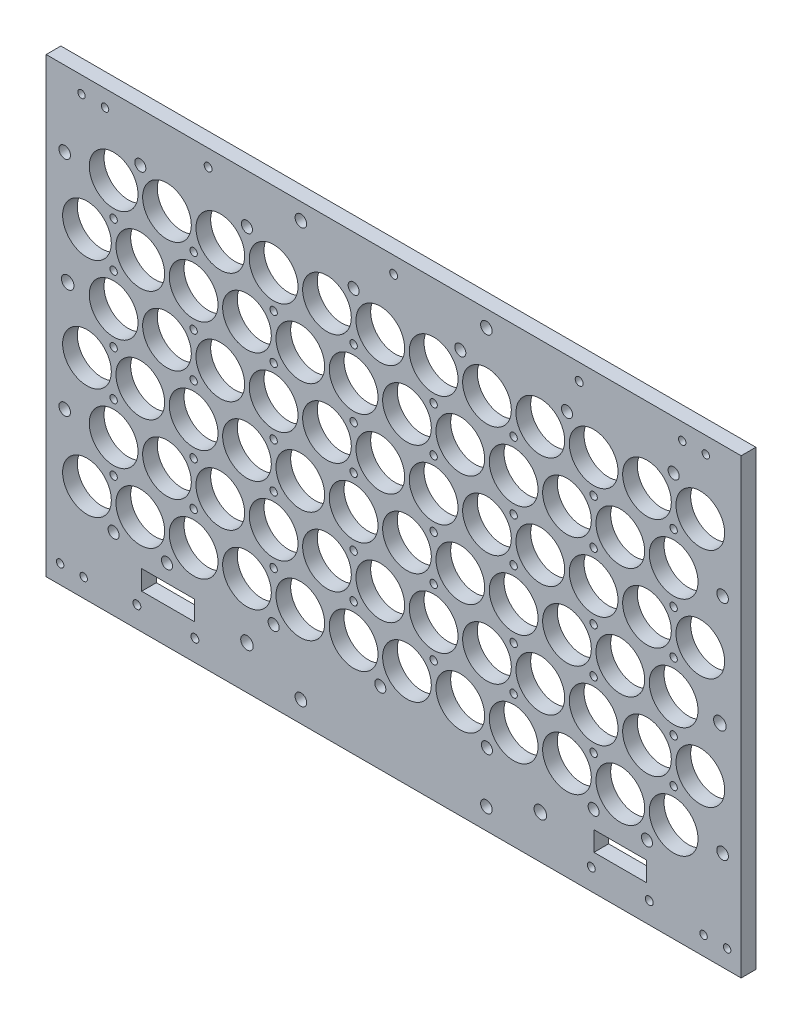
SolidWorks part; units mm, degrees
material "ABS"
ref_plane "X-Y Datum" through (0, 0, 0) normal (0, 0, 1) x (1, 0, 0)
ref_plane "X-Z Datum" through (0, 0, 0) normal (0, 1, 0) x (1, 0, 0)
ref_plane "Y-Z Datum" through (0, 0, 0) normal (1, 0, 0) x (0, 0, -1)
sketch "Sketch1" plane through (0, 0, 0) normal (0, 0, 1) x (1, 0, 0)
  line L1 (-143.025, 70.775) -> (143.025, 70.775)
  line L2 (-143.025, 70.775) -> (-143.025, -70.775)
  line L3 (-143.025, -70.775) -> (143.025, -70.775)
  line L4 (143.025, 70.775) -> (143.025, -70.775)
  line L5 (-143.025, 70.775) -> (143.025, -70.775) construction
  line L6 (-143.025, -70.775) -> (143.025, 70.775) construction
  line L13 (-149.85, -102.6) -> (149.85, -102.6)
  line L14 (-149.85, 91.65) -> (149.85, 91.65)
  line L15 (-149.85, 91.65) -> (-149.85, -102.6)
  line L16 (149.85, 91.65) -> (149.85, -102.6)
  line L17 (149.85, 70.775) -> (149.85, -70.775) construction
  line L18 (-143.025, 91.65) -> (143.025, 91.65) construction
  line L19 (-143.025, -102.6) -> (143.025, -102.6) construction
  line L20 (-149.85, 70.775) -> (-149.85, -70.775) construction
  line L21 (-132.25, -60) -> (-109.25, -60) construction
  circle A0 centre (-132.25, -60) radius 10.775
  circle A1 centre (-109.25, -60) radius 10.775 construction
  circle A2 centre (-120.75, -36) radius 10.775
  point P0 (0, 0)
  point P16 (-120.75, -60)
  dimension "D1" = 21.55
  dimension "D2" = 23
  dimension "D3" = 24
  dimension "D5" = 141.55
  dimension "D6" = 286.05
  dimension "D7" = 31.825
  dimension "D8" = 20.875
  dimension "D9" = 6.825
  dimension "D10" = 6.825
extrude "Boss-Extrude1" add sketch "Sketch1" along normal blind 6.35 contours A0 L3 L4 L1 L2 A2 | A2 | A0 | A0 L2 L3 | L1 L4 L3 L2 region at (2.4105, 0.9241, 0) region at (-140.6182, -68.3682, 0) region at (-132.25, -60, 0) region at (-146.2785, -5.475, 0) region at (-120.75, -36, 0)
sketch "Sketch3" plane through (0, 0, 6.35) normal (0, 0, 1) x (1, 0, 0)
  line L4 (143.025, 70.775) -> (-143.025, 70.775)
  line L5 (143.025, -70.775) -> (143.025, 70.775)
  line L6 (-143.025, -70.775) -> (143.025, -70.775)
  line L7 (-143.025, 70.775) -> (-143.025, -70.775)
  line L8 (143.025, 70.775) -> (-143.025, 70.775)
  line L9 (143.025, -70.775) -> (143.025, 70.775)
  line L10 (-143.025, -70.775) -> (143.025, -70.775)
  line L11 (-143.025, 70.775) -> (-143.025, -70.775)
  circle A0 centre (-132.25, -60) radius 10.4988
  circle A1 centre (-120.75, -36) radius 10.775
  circle A2 centre (-120.75, -36) radius 10.775 construction
  circle A3 centre (-132.25, -60) radius 10.775
  circle A4 centre (-132.25, -60) radius 10.775 construction
  circle A5 centre (-120.75, -36) radius 10.4988
  dimension "D4" = 20.9976
  dimension "D1" = 0
  dimension "D2" = 0
  dimension "D3" = 0
extrude "Cut-Extrude1" cut sketch "Sketch3" against normal through all contours A4 | A0 region at (-132.25, -60, 6.35)
sketch "Sketch4" plane through (0, 0, 6.35) normal (0, 0, 1) x (1, 0, 0)
  line L12 (143.025, 70.775) -> (-143.025, 70.775)
  line L13 (-143.025, 70.775) -> (-143.025, -70.775)
  line L14 (-143.025, -70.775) -> (143.025, -70.775)
  line L15 (143.025, -70.775) -> (143.025, 70.775)
  line L16 (143.025, 70.775) -> (-143.025, 70.775)
  line L17 (-143.025, 70.775) -> (-143.025, -70.775)
  line L18 (-143.025, -70.775) -> (143.025, -70.775)
  line L19 (143.025, -70.775) -> (143.025, 70.775)
  circle A1 centre (-120.75, -36) radius 10.4988
  circle A3 centre (-120.75, -36) radius 10.4988
  circle A5 centre (-132.25, -60) radius 10.4988
  circle A6 centre (-132.25, -60) radius 10.4988
  dimension "D1" = 0
  dimension "D2" = 0
  dimension "D3" = 0
extrude "Cut-Extrude2" cut sketch "Sketch4" against normal through all contours A3 region at (-120.75, -36, 6.35)
pattern_linear "LPattern1" count 12 spacing 23 along (1, 0, 0) of "Cut-Extrude1", "Cut-Extrude2"
pattern_linear "LPattern2" count 3 spacing 48 along (0, 1, 0) of "LPattern1"
sketch "Sketch5" plane through (0, 0, 6.35) normal (0, 0, 1) x (1, 0, 0)
  line L4 (105.3154, -79.3475) -> (90.1846, -79.3475)
  line L5 (90.37, -80.3) -> (90.37, -83.4115)
  line L6 (90.37, -83.4115) -> (105.13, -83.4115)
  line L7 (105.13, -83.4115) -> (105.13, -80.3)
  line L8 (105.3154, -79.3475) -> (90.1846, -79.3475)
  line L9 (90.37, -80.3) -> (90.37, -83.4115)
  line L10 (90.37, -83.4115) -> (105.13, -83.4115)
  line L11 (105.13, -83.4115) -> (105.13, -80.3)
  line L12 (-108.668, -78.95) -> (-108.668, -87.4115)
  line L13 (-108.668, -87.4115) -> (-85.908, -87.4115)
  line L14 (-85.908, -87.4115) -> (-85.908, -78.95)
  line L15 (86.37, -78.95) -> (86.37, -87.4115)
  line L16 (-89.7226, -79.3475) -> (-104.8534, -79.3475)
  line L17 (-104.668, -80.3) -> (-104.668, -83.4115)
  line L18 (-104.668, -83.4115) -> (-89.908, -83.4115)
  line L19 (-89.908, -83.4115) -> (-89.908, -80.3)
  line L20 (-89.7226, -79.3475) -> (-104.8534, -79.3475)
  line L21 (-104.668, -80.3) -> (-104.668, -83.4115)
  line L22 (-104.668, -83.4115) -> (-89.908, -83.4115)
  line L23 (-89.908, -83.4115) -> (-89.908, -80.3)
  line L24 (86.37, -87.4115) -> (109.13, -87.4115)
  line L25 (109.13, -87.4115) -> (109.13, -78.95)
  line L26 (149.85, -78.95) -> (-149.85, -78.95) construction
  line L27 (149.85, -78.95) -> (-149.85, -78.95)
  line L28 (109.13, -87.4115) -> (109.13, -80.3) construction
  line L29 (86.37, -80.3) -> (86.37, -87.4115) construction
  line L30 (-85.908, -87.4115) -> (-85.908, -80.3) construction
  line L31 (-108.668, -80.3) -> (-108.668, -87.4115) construction
  arc A2 (90.37, -80.3) -> (90.1846, -79.3475) centre (87.83, -80.3) ccw
  arc A3 (105.3154, -79.3475) -> (105.13, -80.3) centre (107.67, -80.3) ccw
  arc A4 (90.37, -80.3) -> (90.1846, -79.3475) centre (87.83, -80.3) ccw
  arc A5 (105.3154, -79.3475) -> (105.13, -80.3) centre (107.67, -80.3) ccw
  arc A8 (-104.668, -80.3) -> (-104.8534, -79.3475) centre (-107.208, -80.3) ccw
  arc A9 (-89.7226, -79.3475) -> (-89.908, -80.3) centre (-87.368, -80.3) ccw
  arc A10 (-104.668, -80.3) -> (-104.8534, -79.3475) centre (-107.208, -80.3) ccw
  arc A11 (-89.7226, -79.3475) -> (-89.908, -80.3) centre (-87.368, -80.3) ccw
  dimension "D1" = 0
  dimension "D2" = 0
  dimension "D3" = 4
extrude "Cut-Extrude3" cut sketch "Sketch5" against normal through all contours L25 L27 L15 L24 L8 A5 L11 L10 L9 A4 | A5 L8 A4 L9 L10 L11 | L14 L27 L12 L13 L20 A11 L23 L22 L21 A10 | A11 L20 A10 L21 L22 L23 region at (97.75, -81.376, 6.35) region at (-97.288, -83.9995, 6.35) region at (97.75, -83.9995, 6.35) region at (-97.288, -81.376, 6.35)
sketch "Sketch7" plane through (0, 0, 6.35) normal (0, 0, 1) x (1, 0, 0)
  point P0 (0, 85.3)
  point P1 (80, 85.3)
  point P3 (-124.45, 85.3)
  point P5 (-134.61, 85.3)
  point P7 (-133.6575, -94.6)
  point P9 (-143.8175, -94.6)
  point P11 (133.6575, -94.6)
  point P13 (143.8175, -94.6)
  point P17 (124.45, 85.3)
  point P19 (134.61, 85.3)
  point P21 (110.25, -93.5057)
  point P23 (85.25, -93.5057)
  point P28 (-80, 85.3)
hole_wizard "M3 Clearance Hole1" positions "Sketch8" profile "Sketch9" hole size "M3" standard "ANSI Metric" end condition through all
sketch "Sketch8" plane through (0, 0, 6.35) normal (0, 0, 1) x (1, 0, 0)
  point P3 (124.45, 85.3)
  point P6 (134.61, 85.3)
  point P12 (-124.45, 85.3)
  point P15 (-134.61, 85.3)
  point P18 (-143.8175, -94.6)
  point P21 (-133.6575, -94.6)
  point P24 (133.6575, -94.6)
  point P27 (143.8175, -94.6)
sketch "Sketch9" plane through (124.45, 85.3, 6.35) normal (1, 0, 0) x (0, -1, 0)
  line L0 (0, 0) -> (0, 6.35)
  line L1 (0, 6.35) -> (1.6, 6.35)
  line L2 (1.6, 6.35) -> (1.6, 0)
  line L5 (1.6, 0) -> (0, 0)
  line L11 (0, -6.35) -> (0, 107.95) construction
  dimension "Thru Hole Dia." = 3.2
  dimension "Thru Hole Depth" = 6.35
hole_wizard "M3 Clearance Hole2" positions "Sketch20" profile "Sketch13" hole size "M3" standard "ANSI Metric" end condition through all
sketch "Sketch20" plane through (0, 0, 6.35) normal (0, 0, 1) x (1, 0, 0)
  point P0 (110.25, -93.5057)
  point P3 (85.25, -93.5057)
  point P6 (-80, 85.3)
  point P9 (0, 85.3)
  point P12 (80, 85.3)
sketch "Sketch13" plane through (110.25, -93.5057, 6.35) normal (1, 0, 0) x (0, -1, 0)
  line L0 (0, 0) -> (0, 6.35)
  line L1 (0, 6.35) -> (1.7, 6.35)
  line L2 (1.7, 6.35) -> (1.7, 0)
  line L5 (1.7, 0) -> (0, 0)
  line L11 (0, -6.35) -> (0, 107.95) construction
  dimension "Thru Hole Dia." = 3.4
  dimension "Thru Hole Depth" = 6.35
sketch "Sketch14" plane through (0, 0, 6.35) normal (0, 0, 1) x (1, 0, 0)
  line L0 (131.525, -12) -> (149.85, -12) construction
  line L1 (149.85, 91.65) -> (149.85, -102.6) construction
  line L2 (-131.2488, 12) -> (-149.85, 12) construction
  line L3 (-149.85, 91.65) -> (-149.85, -102.6) construction
  line L4 (149.85, -78.95) -> (-149.85, -78.95) construction
  line L5 (149.85, -78.95) -> (-149.85, -78.95) construction
  line L6 (149.85, -83.95) -> (-149.85, -83.95) construction
  line L7 (68.55, -70.9014) -> (57.95, -70.9014) construction
  line L8 (68.55, -67.0427) -> (68.55, -74.76) construction
  line L9 (57.95, -67.0427) -> (57.95, -74.76) construction
  line L10 (63.25, -70.9014) -> (63.25, -83.95) construction
  line L18 (0, -3.4925) -> (0, 3.4925) construction
  circle A1 centre (-120.75, 12) radius 10.4988 construction
  circle A2 centre (140.6875, -12) radius 2.7
  circle A3 centre (-140.5494, 12) radius 2.7
  circle A4 centre (63.25, -83.95) radius 2.7
  circle A6 centre (-63.25, -83.95) radius 2.7
  circle A8 centre (0, -83.95) radius 2.7
  point P32 (0, 0)
  point P33 (0, 0)
  point P34 (0, 0)
  dimension "D1" = 5.4
  dimension "D3" = 5.4
  dimension "D2" = 5
extrude "Cut-Extrude4" cut sketch "Sketch14" against normal through all contours A6 | A4 | A3 | A2 region at (-140.5494, 12, 6.35) region at (63.25, -83.95, 6.35) region at (-63.25, -83.95, 6.35)
sketch "Sketch15" plane through (0, 0, 6.35) normal (0, 0, 1) x (1, 0, 0)
  line L0 (-6.35, 85.3) -> (86.35, 85.3) construction
  line L1 (-6.35, 90.65) -> (-6.35, 79.95) construction
  line L2 (86.35, 79.95) -> (86.35, 90.65) construction
  line L3 (-86.35, 85.3) -> (6.35, 85.3) construction
  line L4 (-86.35, 90.65) -> (-86.35, 79.95) construction
  line L5 (6.35, 79.95) -> (6.35, 90.65) construction
  line L6 (131.525, 36) -> (149.85, 36) construction
  line L7 (149.85, 94.825) -> (149.85, -105.775) construction
  line L8 (131.525, -60) -> (149.85, -60) construction
  line L9 (-131.2488, -36) -> (-149.85, -36) construction
  line L10 (-149.85, -105.775) -> (-149.85, 94.825) construction
  line L11 (-131.2488, 60) -> (-149.85, 60) construction
  line L12 (-40, 85.3) -> (-40, -102.6) construction
  line L13 (-149.85, -102.6) -> (149.85, -102.6) construction
  line L14 (40, 85.3) -> (40, -102.6) construction
  line L16 (85.25, -93.5057) -> (-85.25, -93.5057) construction
  circle A0 centre (-40, 85.3) radius 2.5
  circle A1 centre (40, 85.3) radius 2.5
  circle A4 centre (141.85, 36) radius 2.5
  circle A5 centre (141.85, -60) radius 2.5
  circle A6 centre (-120.75, -36) radius 10.4988 construction
  circle A7 centre (-120.75, 60) radius 10.4988 construction
  circle A8 centre (-141.85, -36) radius 2.5
  circle A9 centre (-141.85, 60) radius 2.5
  circle A10 centre (-40, -93.5057) radius 2.5
  circle A11 centre (40, -93.5057) radius 2.5
  point P25 (0, 0)
  point P60 (0, 0)
  dimension "D1" = 5
  dimension "D2" = 8
  dimension "D3" = 8
  dimension "D4" = 8
  dimension "D5" = 8
extrude "Cut-Extrude5" cut sketch "Sketch15" against normal through all
sketch "Sketch18" plane through (0, 0, 6.35) normal (0, 0, 1) x (1, 0, 0)
  circle A0 centre (-120.75, -71.41) radius 1.5875 construction
  circle A1 centre (-97.75, -71.41) radius 1.5875 construction
  circle A2 centre (-51.75, -71.41) radius 1.5875 construction
  circle A3 centre (-5.75, -71.41) radius 1.5875 construction
  circle A4 centre (40.25, -71.41) radius 1.5875 construction
  circle A5 centre (-109.25, 71.41) radius 1.5875 construction
  circle A6 centre (-63.25, 71.41) radius 1.5875 construction
  circle A7 centre (-17.25, 71.41) radius 1.5875 construction
  circle A8 centre (28.75, 71.41) radius 1.5875 construction
  circle A9 centre (74.75, 71.41) radius 1.5875 construction
  circle A10 centre (120.75, 71.41) radius 1.5875 construction
  circle A11 centre (86.25, -71.41) radius 1.5875 construction
  circle A12 centre (109.25, -71.41) radius 1.5875 construction
  circle A13 centre (-120.75, -71.41) radius 1.5875 construction
  circle A14 centre (-97.75, -71.41) radius 1.5875 construction
  circle A15 centre (-51.75, -71.41) radius 1.5875 construction
  circle A16 centre (-5.75, -71.41) radius 1.5875 construction
  circle A17 centre (40.25, -71.41) radius 1.5875 construction
  circle A18 centre (-109.25, 71.41) radius 1.5875 construction
  circle A19 centre (-63.25, 71.41) radius 1.5875 construction
  circle A20 centre (-17.25, 71.41) radius 1.5875 construction
  circle A21 centre (28.75, 71.41) radius 1.5875 construction
  circle A22 centre (74.75, 71.41) radius 1.5875 construction
  circle A23 centre (120.75, 71.41) radius 1.5875 construction
  circle A24 centre (86.25, -71.41) radius 1.5875 construction
  circle A25 centre (109.25, -71.41) radius 1.5875 construction
  circle A26 centre (109.25, -71.41) radius 2.3813
  circle A27 centre (86.25, -71.41) radius 2.3813
  circle A28 centre (120.75, 71.41) radius 2.3813
  circle A29 centre (74.75, 71.41) radius 2.3813
  circle A30 centre (28.75, 71.41) radius 2.3813
  circle A31 centre (-17.25, 71.41) radius 2.3812
  circle A32 centre (-63.25, 71.41) radius 2.3812
  circle A33 centre (-109.25, 71.41) radius 2.3813
  circle A34 centre (40.25, -71.41) radius 2.3812
  circle A35 centre (-5.75, -71.41) radius 2.3812
  circle A36 centre (-51.75, -71.41) radius 2.3812
  circle A37 centre (-97.75, -71.41) radius 2.3813
  circle A38 centre (-120.75, -71.41) radius 2.3813
  dimension "D1" = 4.7625
extrude "Cut-Extrude7" cut sketch "Sketch18" against normal through all
sketch "Sketch19" plane through (0, 91.65, 0) normal (0, 1, 0) x (1, 0, 0)
  line L4 (149.85, 0) -> (-149.85, 0)
  line L5 (-149.85, 0) -> (-149.85, -6.35)
  line L6 (-149.85, -6.35) -> (149.85, -6.35)
  line L7 (149.85, -6.35) -> (149.85, 0)
  line L8 (149.85, 0) -> (-149.85, 0)
  line L9 (-149.85, 0) -> (-149.85, -6.35)
  line L10 (-149.85, -6.35) -> (149.85, -6.35)
  line L11 (149.85, -6.35) -> (149.85, 0)
  dimension "D1" = 0
extrude "Boss-Extrude2" add sketch "Sketch19" along normal blind 0.7937
sketch "Sketch22" plane through (0, 0, 6.35) normal (0, 0, 1) x (1, 0, 0)
  line L0 (132.25, -36) -> (120.75, -60) construction
  line L1 (120.75, -60) -> (109.25, -36) construction
  line L2 (109.25, -36) -> (132.25, -36) construction
  line L3 (120.75, -36) -> (120.75, -60) construction
  line L4 (127.7133, -45.468) -> (113.7867, -45.468) construction
  line L5 (109.25, -36) -> (97.75, -60) construction
  line L6 (97.75, -60) -> (86.25, -36) construction
  line L7 (86.25, -36) -> (109.25, -36) construction
  line L8 (97.75, -60) -> (97.75, -36) construction
  line L9 (113.7867, -45.468) -> (90.7867, -45.468) construction
  line L10 (86.25, -36) -> (74.75, -60) construction
  line L11 (74.75, -60) -> (63.25, -36) construction
  line L12 (63.25, -36) -> (86.25, -36) construction
  line L13 (74.75, -36) -> (74.75, -60) construction
  line L14 (90.7867, -45.468) -> (67.7867, -45.468) construction
  line L15 (74.75, -60) -> (97.75, -60) construction
  line L16 (86.25, -36) -> (86.25, -60) construction
  line L17 (79.4061, -50.2829) -> (93.0939, -50.2829) construction
  circle A0 centre (132.25, -36) radius 10.4988 construction
  circle A1 centre (109.25, -36) radius 10.4988 construction
  circle A2 centre (120.75, -45.468) radius 1.5875
  circle A3 centre (86.25, -36) radius 10.4988 construction
  circle A8 centre (86.25, -50.2829) radius 1.5875
  point P34 (0, 0)
  point P35 (0, 0)
  point P38 (0, 0)
  point P39 (0, 0)
  point P40 (0, 0)
  point P41 (0, 0)
  dimension "D1" = 3.175
extrude "Cut-Extrude8" cut sketch "Sketch22" against normal through all
pattern_linear "LPattern3" count 3 spacing 48 along (0, 1, 0) of "Cut-Extrude8"
sketch "Sketch23" plane through (0, 0, 6.35) normal (0, 0, 1) x (1, 0, 0)
  line L0 (132.25, -36) -> (120.75, -12) construction
  line L1 (120.75, -12) -> (109.25, -36) construction
  line L2 (109.25, -36) -> (132.25, -36) construction
  line L3 (120.75, -36) -> (120.75, -12) construction
  line L4 (109.25, -36) -> (97.75, -12) construction
  line L5 (97.75, -12) -> (86.25, -36) construction
  line L6 (86.25, -36) -> (109.25, -36) construction
  line L7 (97.75, -36) -> (97.75, -12) construction
  line L8 (127.7133, -26.532) -> (90.7867, -26.532) construction
  line L9 (86.25, -36) -> (63.25, -36) construction
  line L10 (63.25, -36) -> (74.75, -12) construction
  line L11 (74.75, -12) -> (86.25, -36) construction
  line L12 (74.75, -36) -> (74.75, -12) construction
  line L13 (90.7867, -26.532) -> (67.7867, -26.532) construction
  line L14 (74.75, -12) -> (97.75, -12)
  line L15 (86.25, -12) -> (86.25, -36) construction
  line L16 (79.4061, -21.7171) -> (93.0939, -21.7171) construction
  circle A0 centre (132.25, -36) radius 10.4988 construction
  circle A1 centre (86.25, -36) radius 10.4988 construction
  circle A2 centre (120.75, -26.532) radius 1.5875
  circle A7 centre (86.25, -21.7171) radius 1.5875
  point P31 (0, 0)
  point P32 (0, 0)
  point P33 (0, 0)
  point P34 (0, 0)
  point P35 (0, 0)
  dimension "D1" = 3.175
extrude "Cut-Extrude9" cut sketch "Sketch23" against normal through all contours A7 | A2 region at (120.75, -26.532, 6.35) region at (86.25, -21.7171, 6.35)
pattern_linear "LPattern4" count 2 spacing 48 along (0, 1, 0) of "Cut-Extrude9"
pattern_linear "LPattern5" count 4 spacing 69 along (-1, 0, 0) of "Cut-Extrude8", "LPattern3", "Cut-Extrude9", "LPattern4"
sketch "Sketch25" plane through (0, 0, 6.35) normal (0, 0, 1) x (1, 0, 0)
  line L0 (-85.712, -93.486) -> (-110.712, -93.486)
  line L1 (-149.85, -102.6) -> (149.85, -102.6) construction
  line L3 (-149.85, 92.4437) -> (-149.85, -102.6) construction
  circle A0 centre (-110.712, -93.486) radius 1.5
  circle A1 centre (-85.712, -93.486) radius 1.5
  point P7 (-98.212, -93.486)
  dimension "D1" = 3
  dimension "D2" = 25
  dimension "D3" = 9.114
  dimension "D4" = 39.138
hole_wizard "M3 Clearance Hole3" positions "Sketch30" profile "Sketch29" hole size "M3" standard "ANSI Metric" end condition through all
sketch "Sketch30" plane through (0, 0, 6.35) normal (0, 0, 1) x (1, 0, 0)
  point P0 (-85.712, -93.486)
  point P3 (-110.712, -93.486)
sketch "Sketch29" plane through (-85.712, -93.486, 6.35) normal (1, 0, 0) x (0, -1, 0)
  line L0 (0, 0) -> (0, 6.35)
  line L1 (0, 6.35) -> (1.7, 6.35)
  line L2 (1.7, 6.35) -> (1.7, 0)
  line L5 (1.7, 0) -> (0, 0)
  line L11 (0, -6.35) -> (0, 107.95) construction
  dimension "Thru Hole Dia." = 3.4
  dimension "Thru Hole Depth" = 6.35
